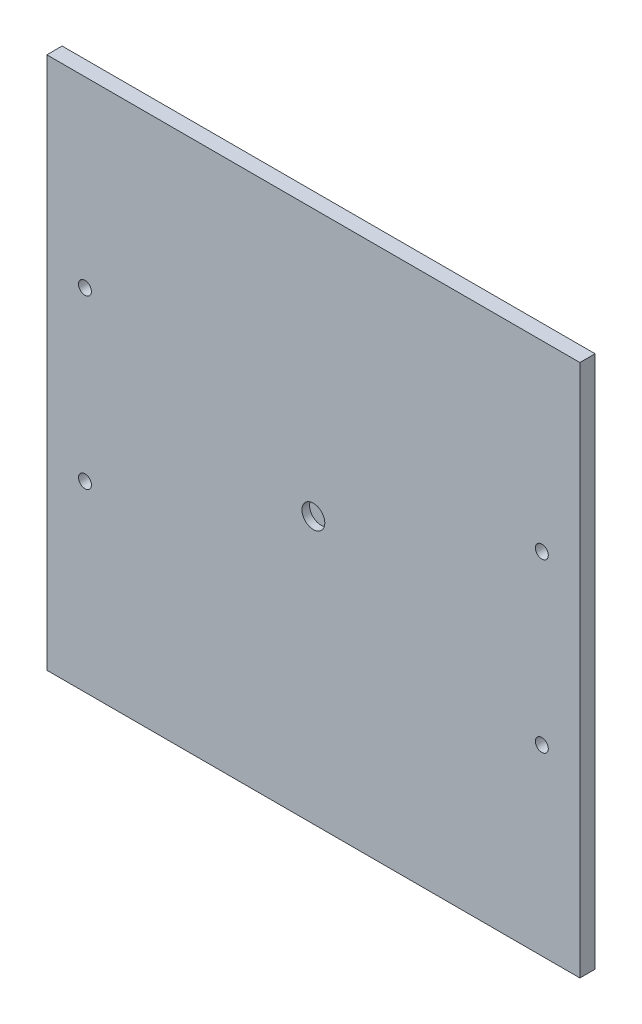
SolidWorks part; units mm, degrees
material "Ceramic Porcelain"
ref_plane "Front Plane" through (0, 0, 0) normal (0, 0, 1) x (1, 0, 0)
ref_plane "Top Plane" through (0, 0, 0) normal (0, 1, 0) x (1, 0, 0)
ref_plane "Right Plane" through (0, 0, 0) normal (1, 0, 0) x (0, 0, -1)
sketch "Sketch1" plane through (0, 0, 0) normal (0, 0, 1) x (1, 0, 0)
  line L0 (140, 70) -> (0, 70) construction
  line L1 (0, 0) -> (140, 0)
  line L2 (0, 0) -> (0, 140)
  line L3 (0, 140) -> (140, 140)
  line L4 (140, 0) -> (140, 140)
  dimension "D1" = 140
  dimension "D5" = 140
extrude "Boss-Extrude1" add sketch "Sketch1" along normal blind 4
hole_wizard "CSK for M3 Flat Head Machine Screw1" positions "Sketch6" profile "Sketch5" countersink size "M3" standard "Ansi Metric" end condition through all
sketch "Sketch6" plane through (0, 0, 0) normal (0, 0, -1) x (-1, 0, 0)
  line L0 (6.0733, 70) -> (-132.5, 70) construction
  line L5 (-130, 92) -> (-130, 48) construction
  line L9 (-70, 140) -> (-70, 0) construction
  line L10 (-140, 140) -> (0, 140) construction
  line L11 (0, 0) -> (-140, 0) construction
  line L13 (-10, 92) -> (-10, 48) construction
  line L14 (-146.0733, 70) -> (-7.5, 70) construction
  point P20 (-130, 92)
  point P22 (-130, 48)
  point P48 (-10, 92)
  point P50 (-10, 48)
  dimension "D1" = 60
  dimension "D3" = 22
  dimension "D4" = 44
sketch "Sketch5" plane through (130, 92, 0) normal (1, 0, 0) x (0, 1, 0)
  line L0 (0, 0) -> (0, 4)
  line L1 (0, 4) -> (1.7, 4)
  line L2 (1.7, 4) -> (1.7, 1.45)
  line L3 (1.7, 1.45) -> (3.15, 0)
  line L5 (3.15, 0) -> (0, 0)
  line L6 (-1.7, 1.45) -> (-3.15, 0) construction
  line L11 (0, -6.35) -> (0, 107.95) construction
  dimension "Thru Hole Dia." = 3.4
  dimension "Thru Hole Depth" = 4
  dimension "Near C'Sink Dia." = 6.3
  dimension "Near C'Sink Angle" = 90
sketch "Sketch7" plane through (0, 0, 0) normal (0, 0, -1) x (-1, 0, 0)
  line L0 (-70, 140) -> (-70, 0) construction
  line L1 (-140, 140) -> (0, 140) construction
  line L2 (0, 0) -> (-140, 0) construction
  line L3 (-61.8, 132) -> (-78.2, 132) construction
  circle A0 centre (-78.2, 132) radius 1.5
  circle A1 centre (-61.8, 132) radius 1.5
  dimension "D2" = 3
  dimension "D3" = 8.2
  dimension "D1" = 8.2
  dimension "D4" = 8
extrude "Cut-Extrude1" [suppressed] cut sketch "Sketch7" against normal through all
sketch "Sketch8" plane through (0, 0, 4) normal (0, 0, -1) x (-1, 0, 0)
  line L0 (-140, 70) -> (0, 70) construction
  line L1 (-140, 0) -> (-140, 140) construction
  line L2 (0, 140) -> (0, 0) construction
  circle A0 centre (-70, 70) radius 3
  dimension "D1" = 6
extrude "Cut-Extrude2" cut sketch "Sketch8" along normal blind 2
